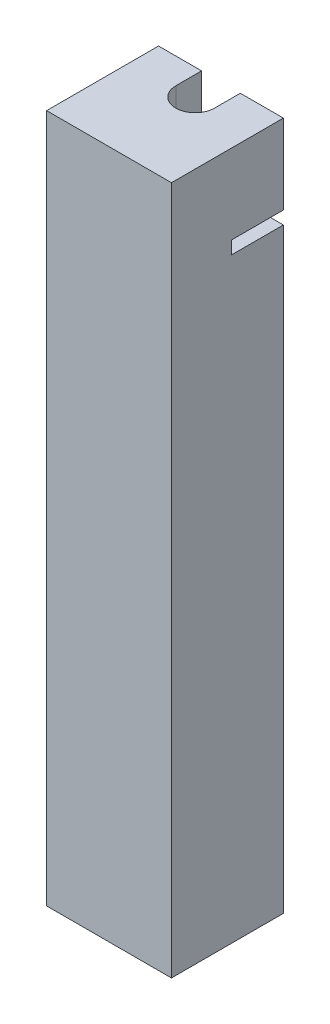
SolidWorks part; units mm, degrees
ref_plane "Front Plane" through (0, 0, 0) normal (0, 0, 1) x (1, 0, 0)
ref_plane "Top Plane" through (0, 0, 0) normal (0, 1, 0) x (1, 0, 0)
ref_plane "Right Plane" through (0, 0, 0) normal (1, 0, 0) x (0, 0, -1)
sketch "Sketch1" plane through (0, 0, 0) normal (0, 1, 0) x (1, 0, 0)
  line L0 (-7.25, 0) -> (7.25, 0) construction
  line L1 (-7.25, 3) -> (-2.25, 3)
  line L2 (-7.25, 3) -> (-7.25, -10)
  line L3 (-7.25, -10) -> (7.25, -10)
  line L4 (7.25, 3) -> (7.25, -10)
  line L5 (-2.25, 0) -> (-2.25, 3)
  line L6 (2.25, 0) -> (2.25, 3)
  line L7 (-2.25, 3) -> (2.25, 3) construction
  line L8 (2.25, 3) -> (7.25, 3)
  arc A0 (-2.25, 0) -> (2.25, 0) centre (0, 0) ccw
  arc A1 (2.25, 0) -> (-2.25, 0) centre (0, 0) ccw construction
  point P13 (0, 0)
  dimension "D1" = 4.5
  dimension "D2" = 5
  dimension "D3" = 3
  dimension "D4" = 10
extrude "Boss-Extrude1" add sketch "Sketch1" along normal mid plane 80
sketch "Sketch2" plane through (0, 0, -3) normal (0, 0, -1) x (-1, 0, 0)
  line L0 (7.25, 40) -> (7.25, -40) construction
  line L1 (-7.25, -40) -> (7.25, -40)
  line L2 (-7.25, -40) -> (-7.25, -30.75)
  line L3 (-7.25, -30.75) -> (7.25, -30.75)
  line L4 (7.25, -40) -> (7.25, -30.75)
  line L5 (-7.25, 40) -> (-7.25, -40) construction
  line L6 (-7.25, 29.25) -> (7.25, 29.25)
  line L7 (-7.25, 29.25) -> (-7.25, 30.75)
  line L8 (-7.25, 30.75) -> (7.25, 30.75)
  line L9 (7.25, 29.25) -> (7.25, 30.75)
  line L10 (-7.25, 30.75) -> (-7.25, 40) construction
  line M6 (-7.25, -40) -> (-2.25, -40)
  line M7 (-2.25, -40) -> (-2.25, 40)
  line M9 (-7.25, 40) -> (-7.25, -40)
  dimension "D1" = 1.5
  dimension "D2" = 60
extrude "Cut-Extrude1" cut sketch "Sketch2" against normal blind 6 contours L6 L9 L8 M7 | L8 L6 M9 M7 region at (4.75, 30, -3) region at (-2.5, 30, -3)
extrude "Boss-Extrude2" add sketch "Sketch2<3>" against normal through all contours L1 L4 L3 M7 | L3 M9 M6 M7 region at (4.75, -35.375, -3) region at (-2.5, -35.375, -3)
sketch "Sketch2<3>" plane through (0, 0, -3) normal (0, 0, -1) x (-1, 0, 0) same geometry as "Sketch2"
sketch "Sketch3" plane through (0, -30.75, 0) normal (0, 1, 0) x (1, 0, 0)
  line L3 (2.25, 0) -> (2.25, 3)
  line L4 (2.25, 3) -> (-2.25, 3)
  line L5 (-2.25, 3) -> (-2.25, 0)
  line L6 (2.25, 0) -> (2.25, 3)
  line L7 (2.25, 3) -> (-2.25, 3)
  line L8 (-2.25, 3) -> (-2.25, 0)
  arc A0 (2.25, 0) -> (-2.25, 0) centre (0, 0) ccw
  arc A1 (-2.25, 0) -> (2.25, 0) centre (0, 0) ccw construction
  arc A3 (-2.25, 0) -> (2.25, 0) centre (0, 0) ccw
  dimension "D1" = 0
extrude "Boss-Extrude3" add sketch "Sketch3" along normal blind 3
equation "\"length\" = 60mm"
equation "\"D1@Boss-Extrude1\"=\"length\"+20"
equation "\"D2@Sketch2\"=\"length\""
